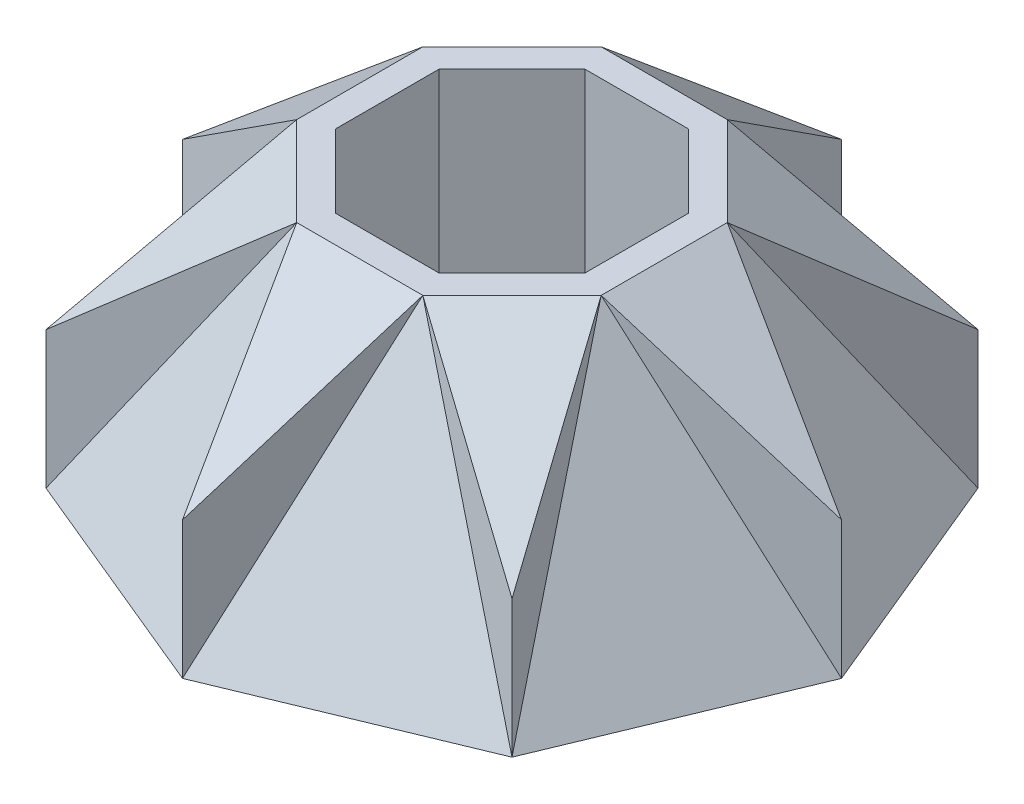
SolidWorks part; units mm, degrees
ref_plane "前视基准面" through (0, 0, 0) normal (0, 0, 1) x (1, 0, 0)
ref_plane "上视基准面" through (0, 0, 0) normal (0, 1, 0) x (1, 0, 0)
ref_plane "右视基准面" through (0, 0, 0) normal (1, 0, 0) x (0, 0, -1)
other "Configuration Table"
sketch "草图3" plane through (0, 0, 0) normal (0, 1, 0) x (1, 0, 0)
  line L0 (0, 0) -> (-79.4485, 0) construction
  line L1 (0, -60) -> (42.4264, -42.4264)
  line L2 (42.4264, -42.4264) -> (60, 0)
  line L3 (60, 0) -> (42.4264, 42.4264)
  line L4 (42.4264, 42.4264) -> (0, 60)
  line L5 (0, 60) -> (-42.4264, 42.4264)
  line L6 (-42.4264, 42.4264) -> (-60, 0)
  line L7 (-60, 0) -> (-42.4264, -42.4264)
  line L8 (-42.4264, -42.4264) -> (0, -60)
  line L9 (11.4805, -27.7164) -> (27.7164, -11.4805)
  line L10 (27.7164, -11.4805) -> (27.7164, 11.4805)
  line L11 (27.7164, 11.4805) -> (11.4805, 27.7164)
  line L12 (11.4805, 27.7164) -> (-11.4805, 27.7164)
  line L13 (-11.4805, 27.7164) -> (-27.7164, 11.4805)
  line L14 (-27.7164, 11.4805) -> (-27.7164, -11.4805)
  line L15 (-27.7164, -11.4805) -> (-11.4805, -27.7164)
  line L16 (-11.4805, -27.7164) -> (11.4805, -27.7164)
  line L17 (-9.4094, 22.7164) -> (-22.7164, 9.4094)
  line L18 (-22.7164, 9.4094) -> (-22.7164, -9.4094)
  line L19 (-22.7164, -9.4094) -> (-9.4094, -22.7164)
  line L20 (-9.4094, -22.7164) -> (9.4094, -22.7164)
  line L21 (9.4094, -22.7164) -> (22.7164, -9.4094)
  line L22 (22.7164, -9.4094) -> (22.7164, 9.4094)
  line L23 (22.7164, 9.4094) -> (9.4094, 22.7164)
  line L24 (9.4094, 22.7164) -> (-9.4094, 22.7164)
  circle A0 centre (0, 0) radius 55.4328 construction
  circle A1 centre (0, 0) radius 27.7164 construction
  dimension "D1" = 120
  dimension "D2" = 60
  dimension "D3" = 5
extrude "凸台-拉伸2" add sketch "草图3" along normal blind 50 contours L7 L8 L1 L2 L3 L4 L5 L6 L16 L15 L14 L13 L12 L11 L10 L9 region at (-20.5638, 0, 49.6453)
ref_plane "基准面1" through (-16.8529, 22.4005, 40.6864) normal (-0.3411, 0.4534, 0.8235) x (0.94, 0.1645, 0.2988)
sketch "草图4" plane through (-16.8529, 22.4005, 40.6864) normal (-0.3411, 0.4534, 0.8235) x (0.94, 0.1645, 0.2988)
  line L1 (-60, 48.9509) -> (60, 48.9509)
  line L2 (-60, 48.9509) -> (-60, -48.9509)
  line L3 (-60, -48.9509) -> (60, -48.9509)
  line L4 (60, 48.9509) -> (60, -48.9509)
  line L5 (-60, 48.9509) -> (60, -48.9509) construction
  line L6 (-60, -48.9509) -> (60, 48.9509) construction
  point P0 (0, 0)
  dimension "D1" = 120
extrude "切除-拉伸1" cut sketch "草图4" along normal blind 50
ref_axis "基准轴1" through (0, 80.4275, 0) along (0, -1, 0)
pattern_circular "阵列(圆周)1" count 8 over 360 about axis through (0, 80.4275, 0) along (0, -1, 0) of "切除-拉伸1"
sketch "草图5" plane through (0, 0, 0) normal (0, 1, 0) x (1, 0, 0)
  line L0 (-27.7164, 11.4805) -> (-60, 0)
  line L1 (-60, 0) -> (-27.7164, -11.4805)
  line L2 (-27.7164, -11.4805) -> (-27.7164, 11.4805)
extrude "凸台-拉伸3" add sketch "草图5" along normal blind 50
sketch "草图6" plane through (0, 0, 0) normal (0, 0, 1) x (1, 0, 0)
  line L0 (-27.7164, 50) -> (-60, 50)
  line L1 (-60, 50) -> (-60, 25)
  line L2 (-60, 50) -> (-60, 0) construction
  line L3 (-60, 25) -> (-27.7164, 50)
extrude "切除-拉伸2" cut sketch "草图6" against normal up to next and the other way up to next
pattern_circular "阵列(圆周)3" count 8 over 360 about axis through (0, 80.4275, 0) along (0, -1, 0) of "凸台-拉伸3", "切除-拉伸2"
extrude "凸台-拉伸4" add sketch "草图3<4>" along normal blind 50 contours L15 L16 L9 L10 L11 L12 L13 L14 L24 L23 L22 L21 L20 L19 L18 L17 region at (0, 0, 26.9324)
sketch "草图3<4>" plane through (0, 0, 0) normal (0, 1, 0) x (1, 0, 0) same geometry as "草图3"
